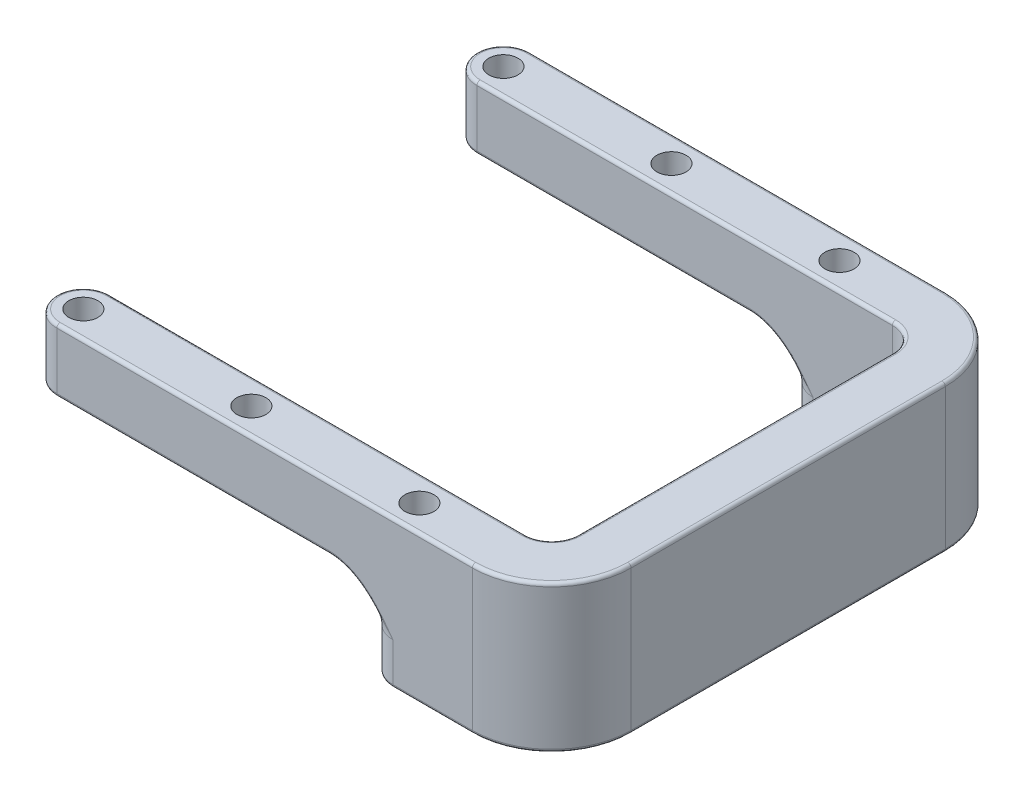
SolidWorks part; units mm, degrees
ref_plane "Front Plane" through (0, 0, 0) normal (0, 0, 1) x (1, 0, 0)
ref_plane "Top Plane" through (0, 0, 0) normal (0, 1, 0) x (1, 0, 0)
ref_plane "Right Plane" through (0, 0, 0) normal (1, 0, 0) x (0, 0, -1)
sketch "Sketch1" plane through (0, 0, 0) normal (0, 1, 0) x (1, 0, 0)
  line L0 (0, 0) -> (70.8, 0)
  line L1 (70.8, 0) -> (70.8, -55.5)
  line L2 (70.8, -55.5) -> (0, -55.5)
  line L3 (0, -55.5) -> (0, -63.5)
  line L4 (0, -63.5) -> (78.8, -63.5)
  line L5 (78.8, -63.5) -> (78.8, 8)
  line L6 (78.8, 8) -> (0, 8)
  line L7 (0, 8) -> (0, 0)
  circle A0 centre (4, 4) radius 2.2
  circle A1 centre (54.8, 4) radius 2.2
  circle A2 centre (4, -59.5) radius 2.2
  circle A3 centre (54.8, -59.5) radius 2.2
  circle A4 centre (29.4, 4) radius 2.2
  circle A5 centre (29.4, -59.5) radius 2.2
  dimension "D5" = 4.4
  dimension "D1" = 8
  dimension "D2" = 8
  dimension "D3" = 4
  dimension "D4" = 4
  dimension "D6" = 50.8
  dimension "D7" = 16
  dimension "D8" = 4
  dimension "D9" = 63.5
  dimension "D10" = 25.4
extrude "Boss-Extrude1" add sketch "Sketch1" along normal blind 22.2504
sketch "Sketch3" plane through (0, 0, 63.5) normal (0, 0, 1) x (1, 0, 0)
  line L1 (0, 0) -> (50.8, 0)
  line L2 (0, 0) -> (0, 12.7)
  line L3 (0, 12.7) -> (50.8, 12.7)
  line L4 (50.8, 0) -> (50.8, 12.7)
  dimension "D1" = 12.7
  dimension "D2" = 50.8
extrude "Cut-Extrude1" cut sketch "Sketch3" against normal through all
fillet "Fillet3" radius 4 10 edges at (0, 17.4752, -8) (0, 17.4752, 0) (0, 17.4752, 55.5) (0, 17.4752, 63.5) (70.8, 11.1252, 0) (70.8, 11.1252, 55.5) (50.8, 6.35, -8) (50.8, 6.35, 0) (50.8, 6.35, 55.5) (50.8, 6.35, 63.5)
fillet "Fillet4" radius 12 2 edges at (78.8, 11.1252, -8) (78.8, 11.1252, 63.5)
fillet "Fillet6" radius 6.35 4 edges at (51.9716, 12.7, -6.8284) (51.9716, 12.7, 56.6716) (51.9716, 12.7, -1.1716) (51.9716, 12.7, 62.3284)
fillet "Fillet5" radius 0.5 40 edges at (60.8, 0, 55.5) (69.6284, 0, 54.3284) (70.8, 0, 27.75) (69.6284, 0, 1.1716) (60.8, 0, 0) (60.8, 0, -8) (75.2853, 0, -4.4853) (78.8, 0, 27.75) (75.2853, 0, 59.9853) (1.1716, 22.2504, 62.3284) (1.1716, 22.2504, 56.6716) (35.4, 22.2504, 55.5) (69.6284, 22.2504, 54.3284) (70.8, 22.2504, 27.75) (69.6284, 22.2504, 1.1716) (35.4, 22.2504, 0) (1.1716, 22.2504, -1.1716) (1.1716, 22.2504, -6.8284) (35.4, 22.2504, -8) (75.2853, 22.2504, -4.4853) (78.8, 22.2504, 27.75) (75.2853, 22.2504, 59.9853) (60.8, 0, 63.5) (35.4, 22.2504, 63.5) (51.9716, 0, 62.3284) (51.9716, 0, 56.6716) (51.9716, 0, -1.1716) (51.9716, 0, -6.8284) (47.8417, 12.2595, 63.5) (47.8417, 12.2595, 55.5) (24.6271, 12.7, 55.5) (1.1716, 12.7, 56.6716) (1.1716, 12.7, 62.3284) (47.8417, 12.2595, -8) (24.6271, 12.7, -8) (1.1716, 12.7, -6.8284) (1.1716, 12.7, -1.1716) (47.8417, 12.2595, 0) (24.6271, 12.7, 63.5) (24.6271, 12.7, 0)
